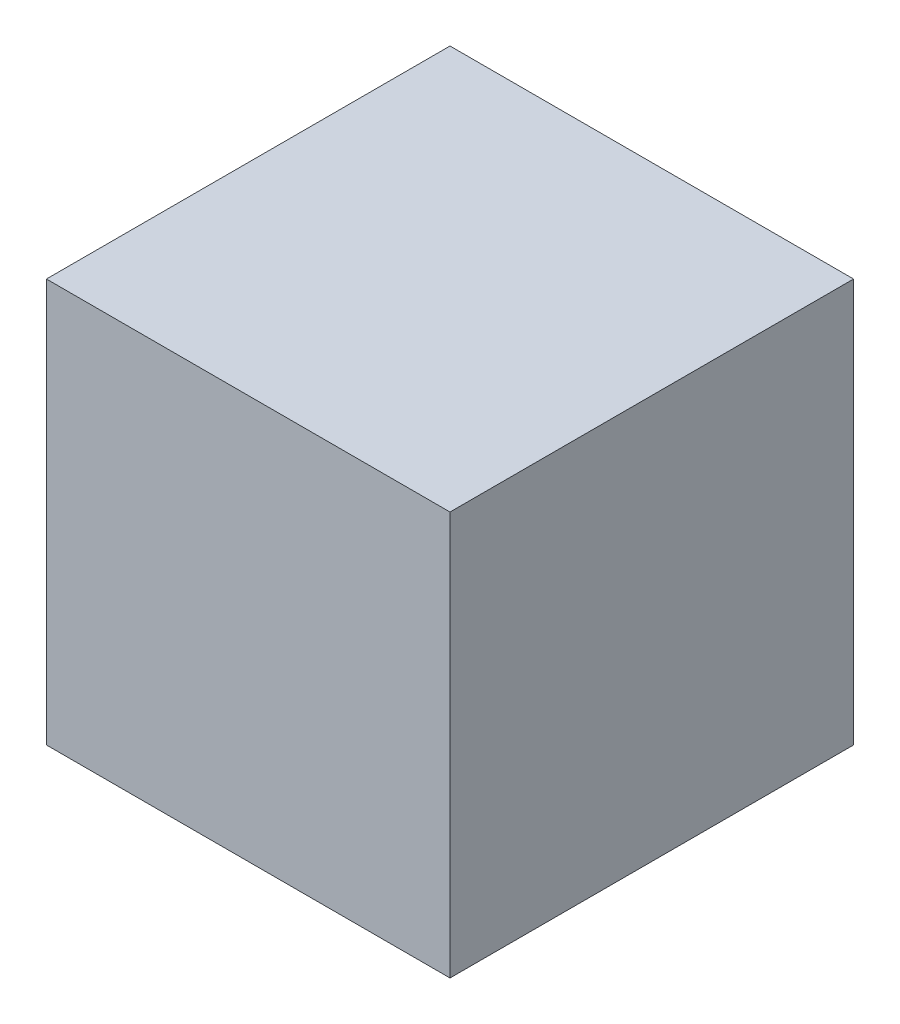
SolidWorks part; units mm, degrees
ref_plane "Спереди" through (0, 0, 0) normal (0, 0, 1) x (1, 0, 0)
ref_plane "Сверху" through (0, 0, 0) normal (0, 1, 0) x (1, 0, 0)
ref_plane "Справа" through (0, 0, 0) normal (1, 0, 0) x (0, 0, -1)
sketch "Sketch1" plane through (0, 0, 0) normal (0, 1, 0) x (1, 0, 0)
  line L1 (-1.5, 1.5) -> (1.5, 1.5)
  line L2 (-1.5, 1.5) -> (-1.5, -1.5)
  line L3 (-1.5, -1.5) -> (1.5, -1.5)
  line L4 (1.5, 1.5) -> (1.5, -1.5)
  line L5 (-1.5, 1.5) -> (1.5, -1.5) construction
  line L6 (-1.5, -1.5) -> (1.5, 1.5) construction
  point P0 (0, 0)
  dimension "D1" = 3
extrude "Boss-Extrude1" add sketch "Sketch1" along normal mid plane 3
